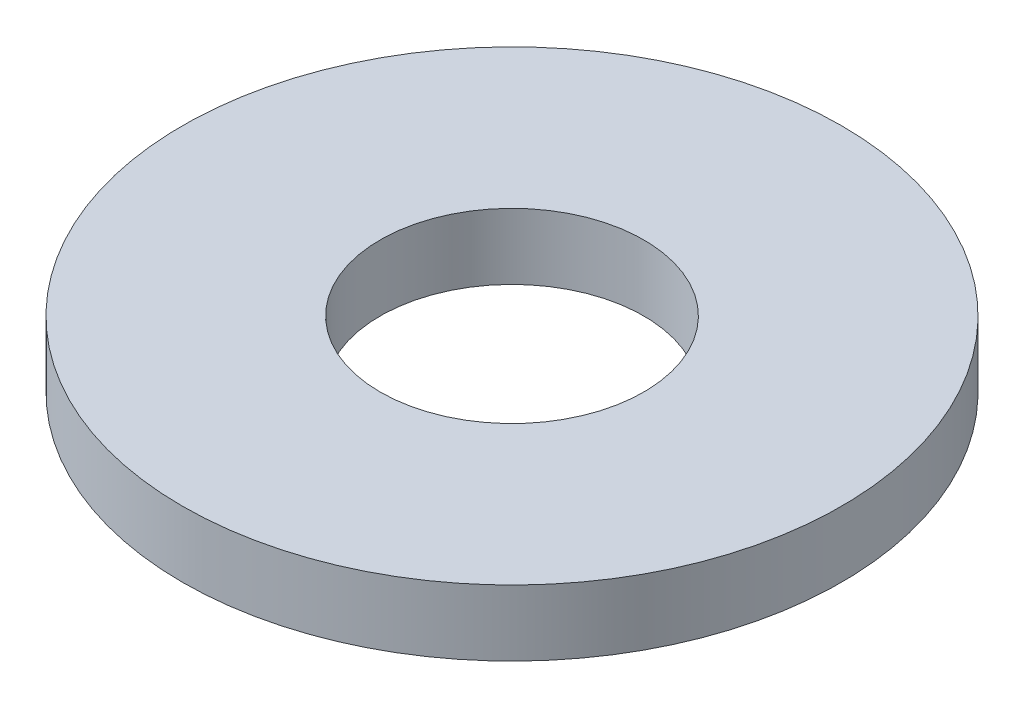
SolidWorks part; units mm, degrees
ref_plane "Front Plane" through (0, 0, 0) normal (0, 0, 1) x (1, 0, 0)
ref_plane "Top Plane" through (0, 0, 0) normal (0, 1, 0) x (1, 0, 0)
ref_plane "Right Plane" through (0, 0, 0) normal (1, 0, 0) x (0, 0, -1)
sketch "Sketch1" plane through (0, 0, 0) normal (0, 1, 0) x (1, 0, 0)
  circle A0 centre (0, 0) radius 75
  dimension "FLANGE_OD" = 150
extrude "Boss-Extrude1" add sketch "Sketch1" along normal blind 15
sketch "Sketch2" plane through (0, 0, 0) normal (0, 1, 0) x (1, 0, 0)
  circle A0 centre (0, 0) radius 30
  dimension "BORE_D" = 60
extrude "Cut-Extrude1" cut sketch "Sketch2" along normal through all
sketch "Sketch3" plane through (0, 15, 0) normal (0, 1, 0) x (1, 0, 0)
  circle A0 centre (0, 0) radius 21.0615 construction
  circle A1 centre (-21.0615, 0) radius 7.1565
  dimension "BOLT_D" = 14.313
  dimension "BOLT_PCD" = 42.1231
extrude "Cut-Extrude2" cut sketch "Sketch3" against normal blind 14.8121 rebuild error yes
pattern_circular "CirPattern1" count 3 over 360 rebuild error yes
